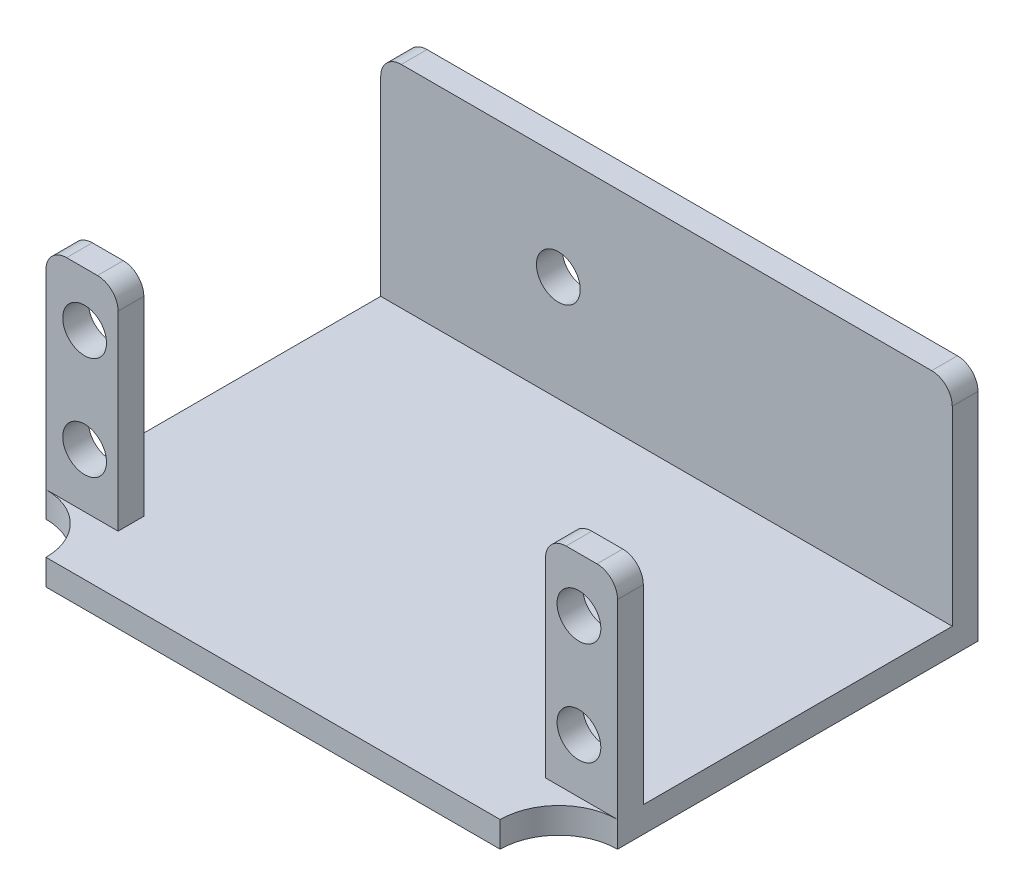
SolidWorks part; units mm, degrees
ref_plane "Front" through (0, 0, 0) normal (0, 0, 1) x (1, 0, 0)
ref_plane "Top" through (0, 0, 0) normal (0, 1, 0) x (1, 0, 0)
ref_plane "Right" through (0, 0, 0) normal (1, 0, 0) x (0, 0, -1)
sketch "Sketch1" plane through (0, 0, 0) normal (0, 1, 0) x (1, 0, 0)
  line L1 (0, 0) -> (55.5, 0)
  line L2 (0, 0) -> (0, 38.2)
  line L3 (0, 38.2) -> (55.5, 38.2)
  line L4 (55.5, 0) -> (55.5, 38.2)
  dimension "D1" = 38.2
  dimension "D2" = 55.5
extrude "bracketBase" add sketch "Sketch1" along normal blind 2.5
ref_plane "referencePlane1" through (0, 0, -8.2) normal (0, 0, 1) x (1, 0, 0)
sketch "Sketch2" plane through (0, 0, -8.2) normal (0, 0, 1) x (1, 0, 0)
  line L0 (27.75, 2.5) -> (27.75, 23) construction
  line L1 (0, 2.5) -> (7, 2.5)
  line L2 (0, 2.5) -> (0, 23)
  line L3 (0, 23) -> (7, 23)
  line L4 (7, 2.5) -> (7, 23)
  line L5 (0, 2.5) -> (55.5, 2.5) construction
  line L6 (55.5, 23) -> (48.5, 23)
  line L7 (48.5, 2.5) -> (48.5, 23)
  line L8 (55.5, 2.5) -> (48.5, 2.5)
  line L9 (55.5, 2.5) -> (55.5, 23)
  dimension "D1" = 20.5
  dimension "D2" = 7
extrude "servoMountingHoleTabs" add sketch "Sketch2" along normal blind 2.5
sketch "Sketch3" plane through (0, 0, -5.7) normal (0, 0, 1) x (1, 0, 0)
  line L0 (0, 12.75) -> (7, 12.75) construction
  line L3 (0, 23) -> (0, 2.5) construction
  line L4 (7, 2.5) -> (7, 23) construction
  line L5 (7, 23) -> (0, 23) construction
  line L6 (27.75, 2.5) -> (27.75, 23) construction
  line L7 (0, 2.5) -> (55.5, 2.5) construction
  circle A0 centre (3.75, 17.75) radius 2.125
  circle A1 centre (3.75, 7.75) radius 2.125
  circle A2 centre (51.75, 7.75) radius 2.125
  circle A3 centre (51.75, 17.75) radius 2.125
  dimension "D1" = 4.25
  dimension "D2" = 3.75
  dimension "D3" = 5.25
extrude "servoMountingHoles" cut sketch "Sketch3" against normal blind 2.5
sketch "Sketch4" plane through (0, 0, 0) normal (0, 1, 0) x (1, 0, 0)
  line L0 (55.5, 8.2) -> (55.5, 38.2) construction
  line L1 (0, 38.2) -> (55.5, 38.2)
  line L2 (0, 38.2) -> (0, 40.7)
  line L3 (0, 40.7) -> (55.5, 40.7)
  line L4 (55.5, 38.2) -> (55.5, 40.7)
  dimension "D1" = 2.5
extrude "baseWall" add sketch "Sketch4" along normal up to surface (23 mm away) up to face at (3.5, 23, -6.95)
sketch "Sketch6" plane through (0, 2.5, 0) normal (0, 1, 0) x (1, 0, 0)
  circle A0 centre (0, 0) radius 5.7
  circle A1 centre (55.5, 0) radius 5.7
extrude "baseTrim" cut sketch "Sketch6" against normal blind 2.5
fillet "Fillet1" radius 2 6 edges at (7, 23, -6.95) (48.5, 23, -6.95) (0, 23, -6.95) (55.5, 23, -6.95) (55.5, 23, -39.45) (0, 23, -39.45)
sketch "Sketch7" plane through (0, 0, -40.7) normal (0, 0, -1) x (-1, 0, 0)
  line L0 (0, 21) -> (0, 0) construction
  line L1 (-55.5, 0) -> (0, 0) construction
  circle A0 centre (-17.25, 12.75) radius 2.125
  dimension "D1" = 4.25
  dimension "D2" = 17.25
  dimension "D3" = 12.75
extrude "M4mountingHole" cut sketch "Sketch7" against normal blind 10
